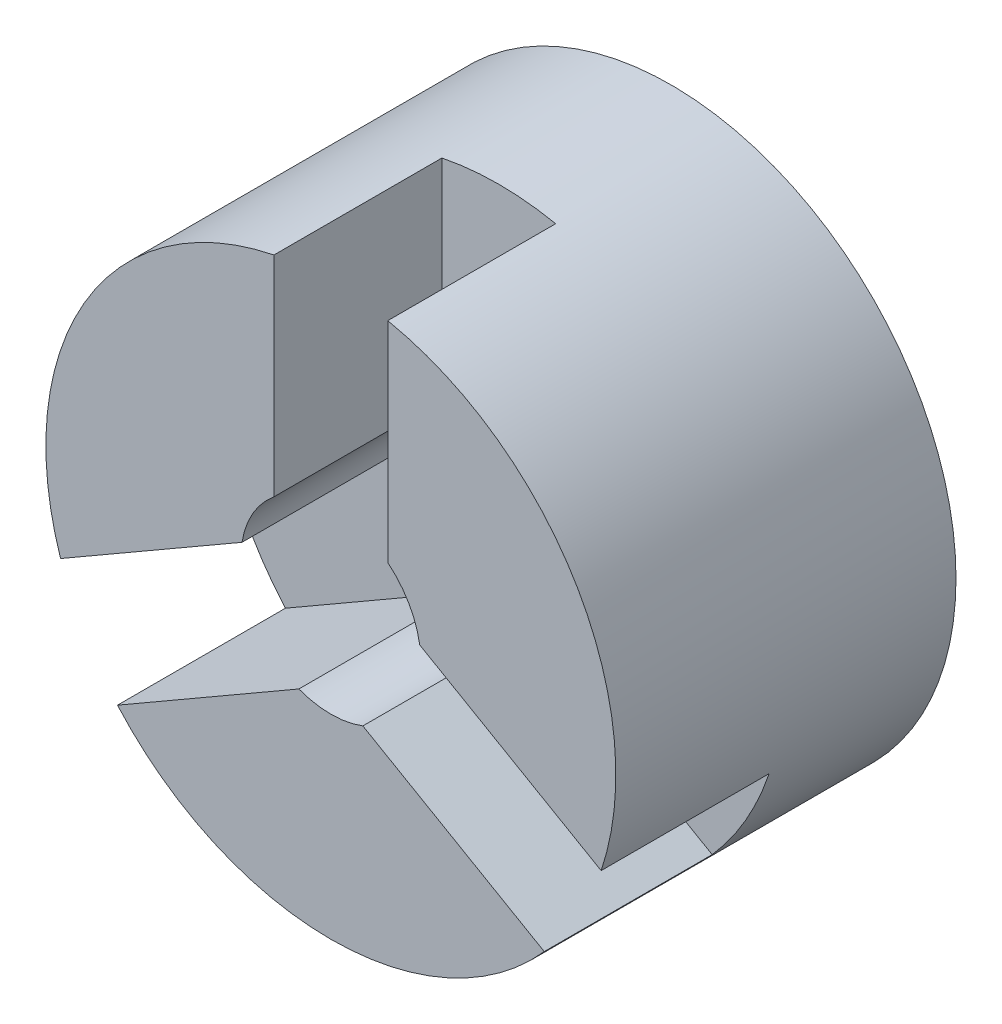
SolidWorks part; units mm, degrees
ref_plane "Front Plane" through (0, 0, 0) normal (0, 0, 1) x (1, 0, 0)
ref_plane "Top Plane" through (0, 0, 0) normal (0, 1, 0) x (1, 0, 0)
ref_plane "Right Plane" through (0, 0, 0) normal (1, 0, 0) x (0, 0, -1)
sketch "Sketch1" plane through (0, 0, 0) normal (0, 0, 1) x (1, 0, 0)
  circle A0 centre (0, 0) radius 15
  dimension "D1" = 30
extrude "Extrude1" add sketch "Sketch1" along normal blind 33
sketch "Sketch2" plane through (0, 0, 0) normal (0, 0, -1) x (-1, 0, 0)
  circle A0 centre (0, 0) radius 7.5
  dimension "D1" = 15
extrude "Cut-Extrude1" cut sketch "Sketch2" against normal blind 3
ref_plane "Plane1" through (0, 0, 5) normal (0, 0, -1) x (-1, 0, 0)
sketch "Sketch3" plane through (0, 0, 5) normal (0, 0, 1) x (1, 0, 0)
  circle A0 centre (0, 0) radius 25
  dimension "D1" = 50
extrude "Extrude2" add sketch "Sketch3" along normal blind 29.84
sketch "Sketch4" plane through (0, 0, 34.84) normal (0, 0, 1) x (1, 0, 0)
  line L0 (0, 0) -> (4.9911, 0)
  line L1 (4.9911, 0) -> (4.9911, 26.8858)
  line L2 (4.9911, 26.8858) -> (-4.9911, 26.8858)
  line L3 (-4.9911, 26.8858) -> (-4.9911, 0)
  line L4 (-4.9911, 0) -> (0, 0)
  dimension "D1" = 9.9822
extrude "Cut-Extrude2" cut sketch "Sketch4" against normal blind 14.732
ref_axis "Axis1" through (0, 0, -1.6599) along (0, 0, 1)
pattern_circular "CirPattern1" count 3 over 360 about axis through (0, 0, -1.6599) along (0, 0, 1) of "Cut-Extrude2"
sketch "Sketch6" plane through (0, 0, 3) normal (0, 0, -1) x (-1, 0, 0)
  circle A0 centre (0, 0) radius 6.5
  dimension "D1" = 13
extrude "Cut-Extrude4" cut sketch "Sketch6" against normal blind 10
sketch "Sketch5" plane through (0, 0, 34.84) normal (0, 0, 1) x (1, 0, 0)
  circle A0 centre (0, 0) radius 7.8994
  dimension "D1" = 15.7988
extrude "Cut-Extrude3" cut sketch "Sketch5" against normal up to surface (21.84 mm away) up to face at (-6.5, 0, 13)
ref_plane "Plane2" through (0, 0, 8) normal (0, 0, 1) x (1, 0, 0)
